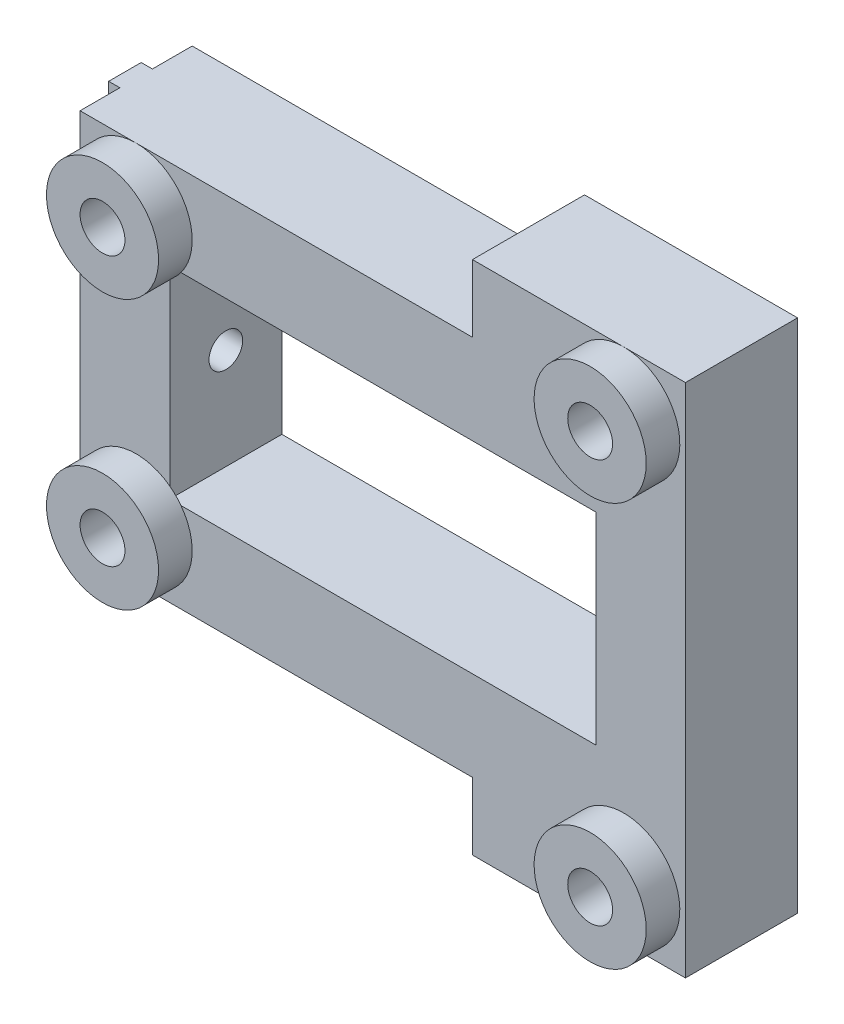
SolidWorks part; units mm, degrees
ref_plane "Plan de face" through (0, 0, 0) normal (0, 0, 1) x (1, 0, 0)
ref_plane "Plan de dessus" through (0, 0, 0) normal (0, 1, 0) x (1, 0, 0)
ref_plane "Plan de droite" through (0, 0, 0) normal (1, 0, 0) x (0, 0, -1)
sketch "Esquisse1" plane through (0, 0, 0) normal (0, 0, 1) x (1, 0, 0)
  line L1 (-27, -23) -> (27, -23)
  line L2 (-27, -23) -> (-27, 23)
  line L3 (-27, 23) -> (27, 23)
  line L4 (27, -23) -> (27, 23)
  point P5 (-35.6467, -23.9889)
  point P7 (0, -23)
  point P8 (-27, 0)
  dimension "D1" = 46
  dimension "D2" = 54
extrude "Boss.-Extru.1" add sketch "Esquisse1" along normal blind 10
sketch "Esquisse2" plane through (0, 0, 10) normal (0, 0, 1) x (1, 0, 0)
  line L1 (-27, -23) -> (27, -23) construction
  line L2 (27, 23) -> (-27, 23) construction
  line L3 (-27, 23) -> (-27, -23) construction
  circle A0 centre (-22, -12) radius 2
  circle A1 centre (-22, 12) radius 2
  circle A2 centre (21.5, 18) radius 2
  circle A3 centre (21.5, -18) radius 2
  dimension "D1" = 4
  dimension "D2" = 48.5
  dimension "D3" = 5
  dimension "D4" = 11
  dimension "D5" = 11
  dimension "D6" = 5
  dimension "D7" = 5
  dimension "D8" = 24
  dimension "D9" = 36
extrude "Enlèv. mat.-Extru.1" cut sketch "Esquisse2" against normal through all
sketch "Esquisse3" plane through (0, 0, 10) normal (0, 0, 1) x (1, 0, 0)
  circle A0 centre (-22, 12) radius 5
  circle A1 centre (-22, -12) radius 5
  circle A2 centre (21.5, -18) radius 5
  circle A3 centre (21.5, 18) radius 5
  circle A4 centre (21.5, 18) radius 2 construction
  circle A5 centre (-22, 12) radius 2 construction
  circle A6 centre (-22, -12) radius 2 construction
  circle A7 centre (21.5, -18) radius 2 construction
  dimension "D1" = 10
extrude "Boss.-Extru.2" add sketch "Esquisse3" along normal blind 3
sketch "Esquisse4" plane through (0, -23, 0) normal (0, -1, 0) x (1, 0, 0)
  line L0 (-27, 10) -> (21.5, 10) construction
  line L1 (8, 10) -> (-27, 10)
  line L2 (8, 10) -> (8, 0)
  line L3 (8, 0) -> (-27, 0)
  line L4 (-27, 10) -> (-27, 0)
  point P6 (-19, 2.2044)
  point P7 (-19, 10)
  point P8 (-27, 0)
  point P10 (0, 0)
  dimension "D2" = 35
extrude "Enlèv. mat.-Extru.2" cut sketch "Esquisse4" against normal blind 6
sketch "Esquisse6" plane through (0, 23, 0) normal (0, 1, 0) x (1, 0, 0)
  line L0 (21.5, -10) -> (-27, -10) construction
  line L1 (-27, 0) -> (8, 0)
  line L2 (-27, 0) -> (-27, -10)
  line L3 (-27, -10) -> (8, -10)
  line L4 (8, 0) -> (8, -10)
  line L5 (-27, -10) -> (-27, 0) construction
  line L6 (27, 0) -> (-27, 0) construction
  line L7 (16.5, -10) -> (26.5, -10) construction
  point P6 (0, 0)
  point P7 (0, 0)
  point P10 (10.75, -10)
  point P13 (0, 0)
  point P14 (8.5157, -10)
  point P17 (-23.0686, 0)
  point P18 (0, 0)
extrude "Enlèv. mat.-Extru.3" cut sketch "Esquisse6" against normal blind 6
sketch "Esquisse7" plane through (-27, 0, 0) normal (-1, 0, 0) x (0, 0, 1)
  line L1 (3.55, 17) -> (6.45, 17)
  line L2 (3.55, 17) -> (3.55, -17)
  line L3 (3.55, -17) -> (6.45, -17)
  line L4 (6.45, 17) -> (6.45, -17)
  line L9 (0, 17) -> (10, 17) construction
  line L10 (10, -17) -> (0, -17) construction
  point P4 (5, 17)
  point P8 (-14.5742, 23)
  point P10 (5, 17)
  dimension "D1" = 2.9
extrude "Boss.-Extru.3" add sketch "Esquisse7" along normal blind 1
sketch "Esquisse10" plane through (0, 0, 10) normal (0, 0, 1) x (1, 0, 0)
  line L0 (-22, 17) -> (8, 17) construction
  line L1 (-19, 9) -> (19, 9)
  line L2 (-19, 9) -> (-19, -9)
  line L3 (-19, -9) -> (19, -9)
  line L4 (19, 9) -> (19, -9)
  line L5 (8, -17) -> (-22, -17) construction
  line L6 (-27, -17) -> (-27, 17) construction
  line L7 (27, -23) -> (27, 23) construction
  dimension "D1" = 8
  dimension "D2" = 8
  dimension "D3" = 8
  dimension "D4" = 8
extrude "Enlèv. mat.-Extru.5" cut sketch "Esquisse10" against normal through all
sketch "Esquisse8" plane through (-28, 0, 0) normal (-1, 0, 0) x (0, 0, 1)
  line L0 (6.45, 17) -> (3.55, 17) construction
  line L1 (3.55, -17) -> (6.45, -17) construction
  line L2 (6.45, -17) -> (6.45, 17) construction
  circle A0 centre (5, 0) radius 1.5
  point P4 (0, 0)
  point P7 (5, 17)
  point P10 (5, -17)
  point P11 (0, 0)
  point P12 (6.45, 0)
  dimension "D1" = 3
extrude "Enlèv. mat.-Extru.4" cut sketch "Esquisse8" against normal up to next
sketch "Esquisse11" plane through (0, 0, 10) normal (0, 0, -1) x (-1, 0, 0)
  circle A0 centre (-21.5, 18) radius 2
  circle A1 centre (22, 12) radius 2
  circle A2 centre (22, -12) radius 2
  circle A3 centre (-21.5, -18) radius 2
  circle A4 centre (-21.5, -18) radius 2 construction
  circle A5 centre (-21.5, 18) radius 2 construction
  circle A6 centre (22, -12) radius 2 construction
  circle A7 centre (22, 12) radius 2 construction
extrude "Enlèv. mat.-Extru.6" cut sketch "Esquisse11" against normal through all
